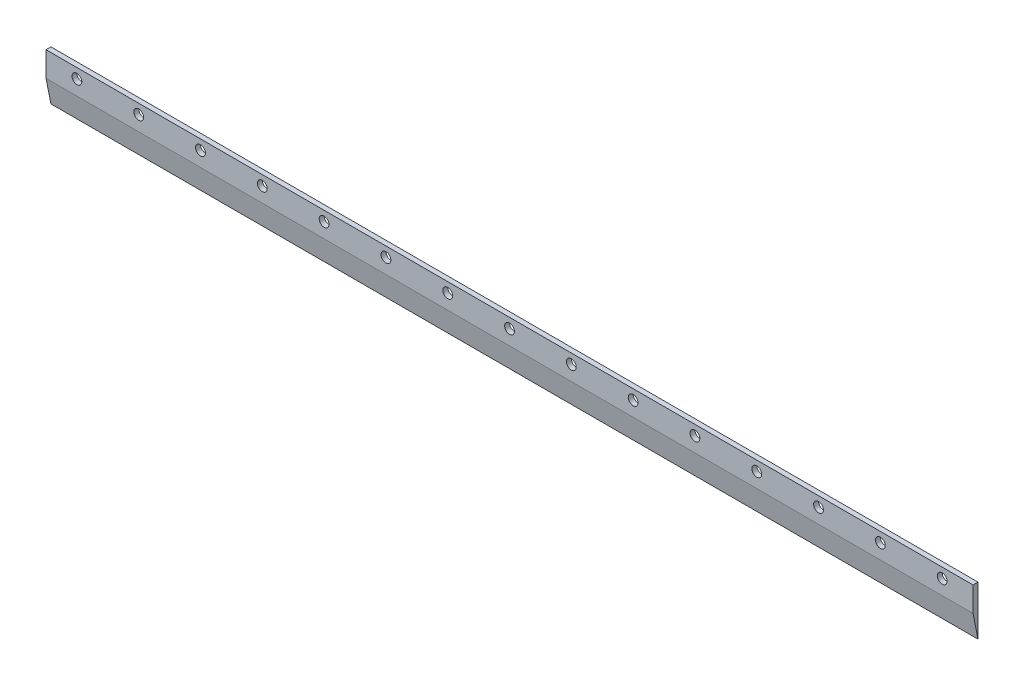
SolidWorks part; units mm, degrees
ref_plane "Alzado" through (0, 0, 0) normal (0, 0, 1) x (1, 0, 0)
ref_plane "Planta" through (0, 0, 0) normal (0, 1, 0) x (1, 0, 0)
ref_plane "Vista lateral" through (0, 0, 0) normal (1, 0, 0) x (0, 0, -1)
sketch "Croquis1" plane through (0, 0, 0) normal (0, 0, 1) x (1, 0, 0)
  line L1 (-375, -20) -> (375, -20)
  line L2 (-375, -20) -> (-375, 20)
  line L3 (-375, 20) -> (375, 20)
  line L4 (375, -20) -> (375, 20)
  line L5 (-375, -20) -> (375, 20) construction
  line L6 (-375, 20) -> (375, -20) construction
  point P0 (0, 0)
  dimension "D1" = 750
  dimension "D2" = 40
extrude "Saliente-Extruir1" add sketch "Croquis1" along normal blind 4
sketch "Croquis2" plane through (375, 0, 0) normal (1, 0, 0) x (0, 0, -1)
  line L0 (0, -20) -> (-4, 0)
  line L1 (-4, -20) -> (-4, 20) construction
  line L2 (-4, 0) -> (0, 0)
  line L3 (0, 0) -> (0, -20)
  line L8 (0, -20) -> (0, 20)
  line L9 (0, 20) -> (-4, 20)
  line L10 (-4, 20) -> (-4, -20)
  line L11 (-4, -20) -> (0, -20)
  line L12 (0, -20) -> (0, 20)
  line L13 (0, 20) -> (-4, 20)
  line L14 (-4, 20) -> (-4, -20)
  line L15 (-4, -20) -> (0, -20)
  line M7 (-4, 20) -> (-4, -20)
  line M8 (-4, -20) -> (0, -20)
  dimension "D1" = 0
extrude "Cortar-Extruir1" cut sketch "Croquis2" against normal through all contours L0 M8 M7 region at (375, -13.3333, 2.6667)
sketch "Croquis3" plane through (0, 0, 0) normal (0, 0, -1) x (-1, 0, 0)
  line L0 (449.2914, 0) -> (-432.142, 0) construction
  line L1 (-432.142, 12) -> (449.2914, 12) construction
  line L2 (0, 47.4243) -> (0, -46.0865) construction
  line L4 (-350, 12) -> (-300, 12) construction
  circle A0 centre (-350, 12) radius 3.9688
  circle A1 centre (-300, 12) radius 3.9688
  circle A2 centre (-250, 12) radius 3.9688
  circle A3 centre (-200, 12) radius 3.9688
  circle A4 centre (-150, 12) radius 3.9688
  circle A5 centre (-100, 12) radius 3.9688
  circle A6 centre (-50, 12) radius 3.9688
  circle A7 centre (0, 12) radius 3.9688
  circle A8 centre (50, 12) radius 3.9688
  circle A9 centre (100, 12) radius 3.9688
  circle A10 centre (150, 12) radius 3.9688
  circle A11 centre (200, 12) radius 3.9688
  circle A12 centre (250, 12) radius 3.9688
  circle A13 centre (300, 12) radius 3.9688
  circle A14 centre (350, 12) radius 3.9688
  point P7 (0, 0)
  dimension "D3" = 7.9375
  dimension "D1" = 12
  dimension "D5" = 50
  dimension "D4" = 15
extrude "Cortar-Extruir2" cut sketch "Croquis3" against normal blind 10
